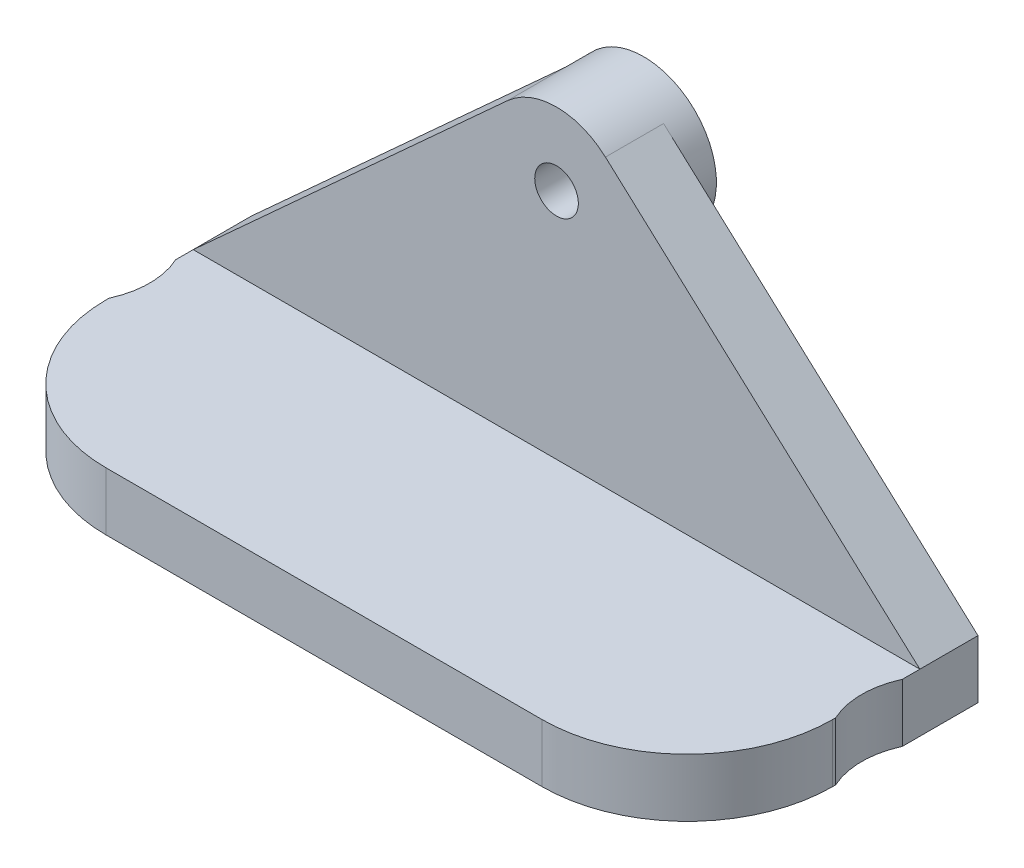
SolidWorks part; units mm, degrees
ref_plane "Alzado" through (0, 0, 0) normal (0, 0, 1) x (1, 0, 0)
ref_plane "Planta" through (0, 0, 0) normal (0, 1, 0) x (1, 0, 0)
ref_plane "Vista lateral" through (0, 0, 0) normal (1, 0, 0) x (0, 0, -1)
sketch "Croquis1" plane through (0, 0, 0) normal (0, 1, 0) x (1, 0, 0)
  line L1 (-25, -10) -> (25, -10)
  line L2 (-25, -10) -> (-25, 10)
  line L3 (-25, 10) -> (25, 10)
  line L4 (25, -10) -> (25, 10)
  line L5 (-25, -10) -> (25, 10) construction
  line L6 (-25, 10) -> (25, -10) construction
  point P0 (0, 0)
  dimension "D1" = 50
  dimension "D2" = 20
extrude "Saliente-Extruir1" add sketch "Croquis1" along normal blind 4
sketch "Croquis2" plane through (0, 0, -10) normal (0, 0, -1) x (-1, 0, 0)
  line L0 (0, 55) -> (0, -55) construction
  line L1 (-25, 4) -> (-3.3662, 23.6971)
  line L2 (25, 4) -> (3.3662, 23.6971)
  line L3 (25, 4) -> (25, 0) construction
  line L4 (-25, 4) -> (25, 4)
  line L5 (-25, 4) -> (-25, 0) construction
  line L6 (55, 0) -> (-55, 0) construction
  line L9 (-25, 4) -> (25, 4) construction
  circle A0 centre (0, 20) radius 5
  circle A1 centre (0, 20) radius 1.5
  line M3 (25, 4) -> (-25, 4)
  dimension "D1" = 10
  dimension "D3" = 3
  dimension "D2" = 20
extrude "Saliente-Extruir4" add sketch "Croquis2" against normal blind 4 contours A0 L1 L2 M3 | A0 A1 region at (0, 10.1062, -10) region at (0, 24.8586, -10)
extrude "Saliente-Extruir5" add sketch "Croquis2<3>" along normal blind 2 contours A0 A1 region at (0, 24.8586, -10)
sketch "Croquis2<3>" plane through (0, 0, -10) normal (0, 0, -1) x (-1, 0, 0) same geometry as "Croquis2"
sketch "Croquis5" plane through (0, 4, 0) normal (0, 1, 0) x (1, 0, 0)
  line L0 (0, 23.0787) -> (0, -34.743) construction
  line L1 (0, -55) -> (0, 55) construction
  line L2 (-25, -10) -> (25, -10) construction
  circle A0 centre (-30, 2.5) radius 5.5
  circle A1 centre (30, 2.5) radius 5.5
  dimension "D1" = 60
  dimension "D2" = 11
  dimension "D3" = 12.5
extrude "Cortar-Extruir1" cut sketch "Croquis5" against normal up to next
fillet "Redondeo1" radius 10 2 edges at (25, 2, 10) (-25, 2, 10)
